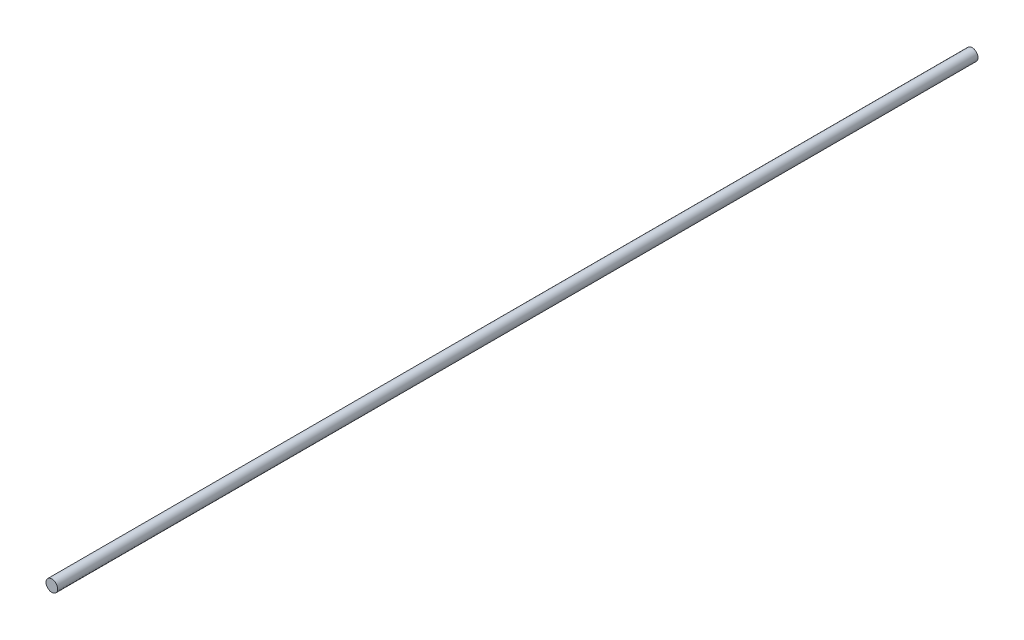
SolidWorks part; units mm, degrees
ref_plane "Front Plane" through (0, 0, 0) normal (0, 0, 1) x (1, 0, 0)
ref_plane "Top Plane" through (0, 0, 0) normal (0, 1, 0) x (1, 0, 0)
ref_plane "Right Plane" through (0, 0, 0) normal (1, 0, 0) x (0, 0, -1)
sketch "Sketch1" plane through (0, 0, 0) normal (0, 0, 1) x (1, 0, 0)
  circle A0 centre (0, 0) radius 0.975
  dimension "D1" = 1.95
extrude "Boss-Extrude1" add sketch "Sketch1" along normal blind 153.75
